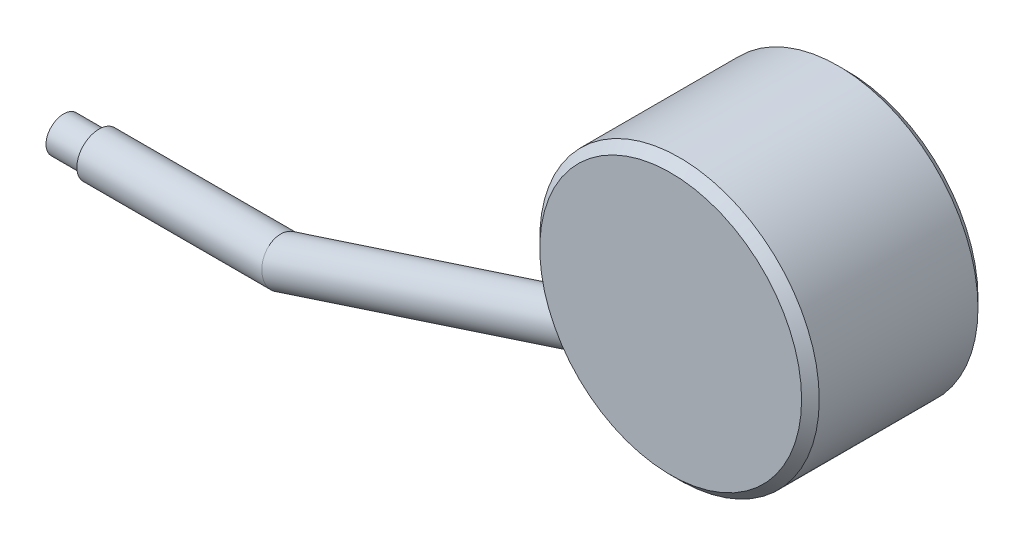
SolidWorks part; units mm, degrees
ref_plane "Front Plane" through (0, 0, 0) normal (0, 0, 1) x (1, 0, 0)
ref_plane "Top Plane" through (0, 0, 0) normal (0, 1, 0) x (1, 0, 0)
ref_plane "Right Plane" through (0, 0, 0) normal (1, 0, 0) x (0, 0, -1)
sketch "Sketch1" plane through (0, 0, 0) normal (0, 0, 1) x (1, 0, 0)
  line L0 (0, 0) -> (50, 0)
  line L1 (50, 0) -> (145.0551, 31.0569)
  dimension "D1" = 50
  dimension "D2" = 100
sketch "Sketch2" plane through (0, 0, 0) normal (1, 0, 0) x (0, 0, -1)
  circle A0 centre (0, 0) radius 5
  dimension "D1" = 10
sweep "Sweep1" add profiles "Sketch2" path "Sketch1"
sketch "Sketch3" plane through (0, 0, 0) normal (0, 0, 1) x (1, 0, 0)
  circle A0 centre (157.656, 51.5743) radius 31.6867
extrude "Boss-Extrude1" add sketch "Sketch3" along normal blind 20 and the other way blind 20
sketch "Sketch4" plane through (0, 0, 0) normal (-1, 0, 0) x (0, 0, 1)
  circle A0 centre (0, 0) radius 4
  circle A1 centre (0, 0) radius 8.0789
  dimension "D1" = 8
extrude "Cut-Extrude1" cut sketch "Sketch4" against normal blind 8
chamfer "Chamfer1" distance 2 angle 45 2 edges at (189.3427, 51.5743, 20) (189.3427, 51.5743, -20)
